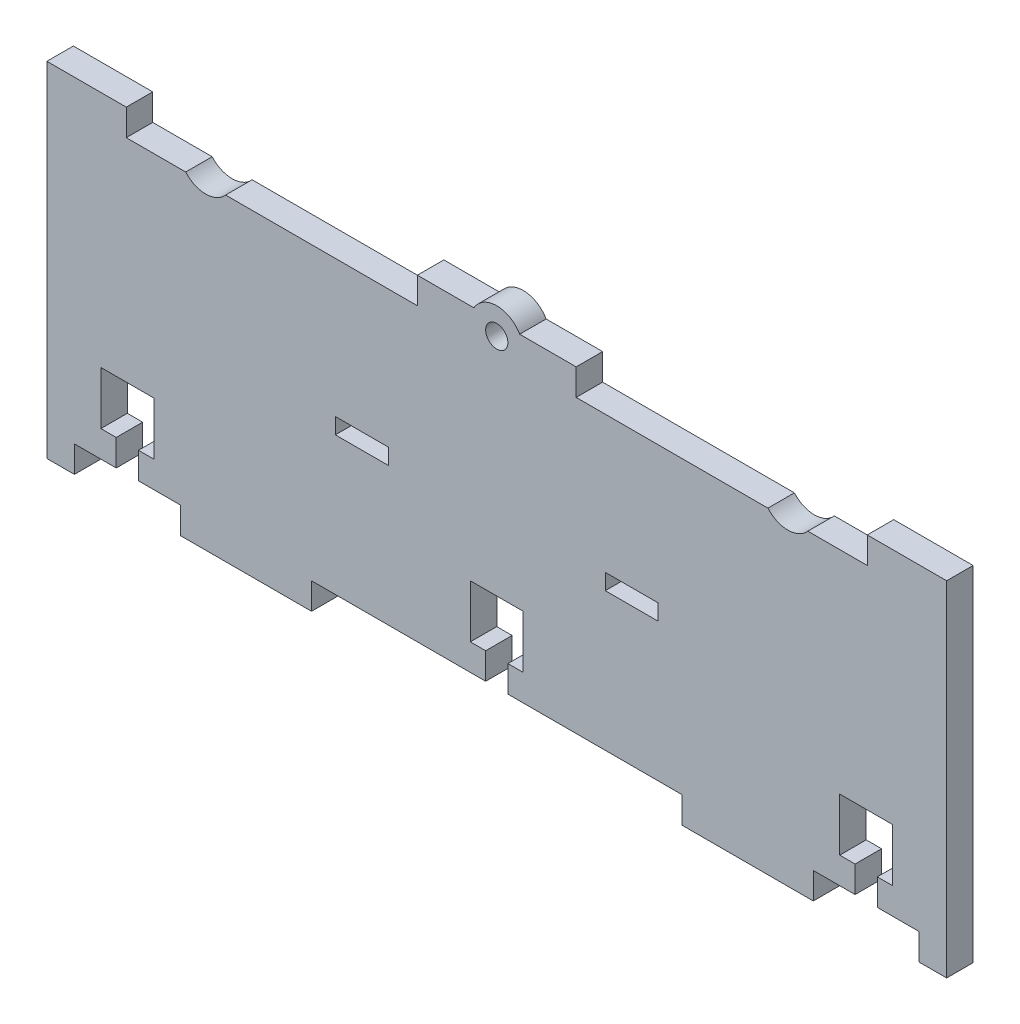
SolidWorks part; units mm, degrees
ref_plane "Front Plane" through (0, 0, 0) normal (0, 0, 1) x (1, 0, 0)
ref_plane "Top Plane" through (0, 0, 0) normal (0, 1, 0) x (1, 0, 0)
ref_plane "Right Plane" through (0, 0, 0) normal (1, 0, 0) x (0, 0, -1)
sketch "Sketch1" plane through (0, 0, 0) normal (0, 0, 1) x (1, 0, 0)
  line L0 (35, 0) -> (35, -5)
  line L1 (115, 0) -> (-115, 0)
  line L2 (0, 0) -> (0, 55) construction
  line L3 (115, 55) -> (-115, 55)
  line L4 (-115, 0) -> (-115, 55)
  line L5 (-115, 15) -> (-120, 15)
  line L6 (-115, 15) -> (-115, 40)
  line L7 (-115, 40) -> (-120, 40)
  line L8 (-120, 15) -> (-120, 40)
  line L9 (-100, 55) -> (-70, 55)
  line L10 (-100, 55) -> (-100, 60)
  line L11 (-100, 60) -> (-70, 60)
  line L12 (-70, 55) -> (-70, 60)
  line L13 (-95, 0) -> (-35, 0)
  line L14 (-95, 0) -> (-95, -5)
  line L15 (-95, -5) -> (-35, -5)
  line L16 (-35, 0) -> (-35, -5)
  line L17 (95, -5) -> (35, -5)
  line L18 (95, 0) -> (95, -5)
  line L19 (95, 0) -> (35, 0)
  line L20 (70, 55) -> (70, 60)
  line L21 (100, 60) -> (70, 60)
  line L22 (100, 55) -> (100, 60)
  line L23 (100, 55) -> (70, 55)
  line L24 (120, 15) -> (120, 40)
  line L25 (115, 40) -> (120, 40)
  line L26 (115, 15) -> (115, 40)
  line L27 (115, 15) -> (120, 15)
  line L28 (115, 0) -> (115, 55)
  point P9 (-120, 27.5)
  point P10 (0, 27.5)
  dimension "D1" = 115
  dimension "D2" = 55
  dimension "D3" = 5
  dimension "D4" = 25
  dimension "D5" = 30
  dimension "D6" = 15
  dimension "D7" = 5
  dimension "D8" = 5
  dimension "D9" = 60
  dimension "D10" = 20
extrude "Boss-Extrude1" add sketch "Sketch1" along normal blind 5 contours L1 L2 L3 L4 | L3 L22 L21 L20 | L18 L1 L0 L17 | L3 L12 L11 L10 | L16 L1 L14 L15 | L8 L5 L4 L7 | L3 L4 L1 L28 | L26 L25 L24 L27 region at (65, -2.5, 0) region at (-57.5, 27.5, 0) region at (-65, -2.5, 0) region at (85, 57.5, 0) region at (-85, 57.5, 0) region at (-117.5, 27.5, 0)
sketch "Sketch2" plane through (0, 0, 0) normal (0, 0, -1) x (-1, 0, 0)
  line L0 (120, 15) -> (120, 40) construction
  line L1 (85, -5) -> (120, -5)
  line L2 (85, -5) -> (85, 60)
  line L3 (85, 60) -> (120, 60)
  line L4 (120, -5) -> (120, 60)
  line L6 (95, -5) -> (35, -5) construction
  line L7 (0, 28.4281) -> (0, 15.5246) construction
  line L8 (-120, -5) -> (-120, 60)
  line L9 (-85, 60) -> (-120, 60)
  line L10 (-85, -5) -> (-85, 60)
  line L11 (-85, -5) -> (-120, -5)
  dimension "D1" = 35
  dimension "D2" = 35
  dimension "D3" = 65
extrude "Cut-Extrude1" cut sketch "Sketch2" against normal blind 10
sketch "Sketch3" plane through (0, 0, 0) normal (0, 0, -1) x (-1, 0, 0)
  line L0 (-70, 55) -> (70, 55) construction
  line L1 (-58.7707, 55) -> (-51.2293, 55)
  line L2 (0, 55) -> (0, 47.8155) construction
  line L3 (58.7707, 55) -> (51.2293, 55)
  line L5 (85, 60) -> (85, -5) construction
  arc A0 (-58.7707, 55) -> (-51.2293, 55) centre (-55, 58.2836) ccw
  arc A2 (58.7707, 55) -> (51.2293, 55) centre (55, 58.2836) cw
  line M7 (70, 55) -> (-70, 55)
  dimension "D1" = 5
  dimension "D2" = 26.2293
  dimension "D3" = 30
extrude "Cut-Extrude2" cut sketch "Sketch3" against normal blind 5 contours A2 M7 | L1 A0 region at (-55, 54.3022, 0)
sketch "Sketch4" plane through (0, 55, 0) normal (0, 1, 0) x (1, 0, 0)
  line L0 (51.2293, 0) -> (-51.2293, 0) construction
  line L1 (15, 0) -> (-15, 0)
  line L2 (15, 0) -> (15, -5)
  line L3 (15, -5) -> (-15, -5)
  line L4 (-15, 0) -> (-15, -5)
  line L5 (51.2293, -5) -> (-51.2293, -5) construction
  point P8 (0, 0)
  dimension "D1" = 30
  dimension "D2" = 15
extrude "Boss-Extrude2" add sketch "Sketch4" along normal blind 5
sketch "Sketch5" plane through (0, 0, 0) normal (0, 0, -1) x (-1, 0, 0)
  line L0 (-85, -5) -> (-35, -5) construction
  line L1 (-59.8, -5) -> (-79.8, -5)
  line L2 (-59.8, -5) -> (-59.8, 0)
  line L3 (-59.8, 0) -> (-79.8, 0)
  line L4 (-79.8, -5) -> (-79.8, 0)
  line L5 (-85, -5) -> (-85, 60) construction
  line L6 (0, 0) -> (0, 22.2278) construction
  line L7 (-35, 0) -> (35, 0) construction
  line L8 (79.8, -5) -> (79.8, 0)
  line L9 (59.8, 0) -> (79.8, 0)
  line L10 (59.8, -5) -> (59.8, 0)
  line L11 (59.8, -5) -> (79.8, -5)
  dimension "D1" = 20
  dimension "D2" = 5.2
extrude "Cut-Extrude3" cut sketch "Sketch5" against normal blind 5
sketch "Sketch6" plane through (0, 0, 0) normal (0, 0, -1) x (-1, 0, 0)
  line L0 (-15, 60) -> (15, 60) construction
  circle A0 centre (0, 57.5) radius 2.1
  dimension "D1" = 2.5
  dimension "D2" = 4.2
extrude "Cut-Extrude4" cut sketch "Sketch6" against normal blind 5
sketch "Sketch7" plane through (0, 0, 0) normal (0, 0, -1) x (-1, 0, 0)
  line L0 (-15, 60) -> (15, 60) construction
  line L1 (4.3301, 60) -> (-4.3301, 60)
  arc A0 (-4.3301, 60) -> (4.3301, 60) centre (0, 57.5) cw
  dimension "D1" = 5
extrude "Boss-Extrude3" add sketch "Sketch7" against normal blind 5
sketch "Sketch8" plane through (0, 0, 0) normal (0, 0, -1) x (-1, 0, 0)
  line L0 (79.8, 0) -> (59.8, 0) construction
  line L1 (67.7, 0) -> (71.9, 0)
  line L2 (67.7, 0) -> (67.7, 5)
  line L3 (67.7, 5) -> (71.9, 5)
  line L4 (71.9, 0) -> (71.9, 5)
  line L5 (0, 0) -> (0, 16.7932) construction
  line L6 (74.8, 5) -> (64.8, 5)
  line L7 (74.8, 5) -> (74.8, 15)
  line L8 (74.8, 15) -> (64.8, 15)
  line L9 (64.8, 5) -> (64.8, 15)
  line L10 (-64.8, 5) -> (-64.8, 15)
  line L11 (-74.8, 15) -> (-64.8, 15)
  line L12 (-74.8, 5) -> (-74.8, 15)
  line L13 (-74.8, 5) -> (-64.8, 5)
  line L14 (-71.9, 0) -> (-71.9, 5)
  line L15 (-67.7, 5) -> (-71.9, 5)
  line L16 (-67.7, 0) -> (-67.7, 5)
  line L17 (-67.7, 0) -> (-71.9, 0)
  line L18 (-35, 0) -> (35, 0) construction
  line L19 (-2.1, 0) -> (2.1, 0)
  line L20 (-2.1, 0) -> (-2.1, 5)
  line L21 (-2.1, 5) -> (2.1, 5)
  line L22 (2.1, 0) -> (2.1, 5)
  line L24 (-5, 5) -> (5, 5)
  line L25 (-5, 5) -> (-5, 15)
  line L26 (-5, 15) -> (5, 15)
  line L27 (5, 5) -> (5, 15)
  point P10 (69.8, 5)
  point P11 (69.8, 0)
  point P12 (69.8, 15)
  point P34 (0, 15)
  point P35 (0, 0)
  line M19 (-79.8, 0) -> (-59.8, 0)
  line M23 (-35, 0) -> (35, 0)
  line M27 (59.8, 0) -> (79.8, 0)
  dimension "D1" = 5
  dimension "D2" = 4.2
  dimension "D3" = 10
  dimension "D4" = 10
  dimension "D5" = 5
  dimension "D6" = 10
  dimension "D7" = 10
  dimension "D8" = 4.2
extrude "Cut-Extrude5" cut sketch "Sketch8" against normal blind 5 contours L12 L13 L10 L11 | L16 L13 L14 M19 | L5 L24 L27 L26 | L21 L5 L26 L25 L24 | L5 L19 L22 L24 | L5 L21 L20 M23 | L9 L6 L3 L7 L8 | L4 L3 L2 M27 region at (-69.8, 2.5, 0) region at (-69.8, 10, 0) region at (1.05, 2.5, 0) region at (-1.05, 2.5, 0) region at (2.5, 10, 0) region at (-2.5, 10, 0) region at (69.8, 10, 0) region at (69.8, 2.5, 0)
sketch "Sketch9" plane through (0, 0, 0) normal (0, 0, -1) x (-1, 0, 0)
  line L0 (-20.5, 27.7965) -> (-42.5, 27.7965) construction
  line L1 (-20.5, 27.7965) -> (-42.5, 27.7965) construction
  line L2 (0, 57.5) -> (0, 41.2875) construction
  line L3 (-30.5, 26.1252) -> (-20.5, 26.1252)
  line L4 (-30.5, 26.1252) -> (-30.5, 29.1252)
  line L5 (-30.5, 29.1252) -> (-20.5, 29.1252)
  line L6 (-20.5, 26.1252) -> (-20.5, 29.1252)
  line L7 (20.5, 26.1252) -> (20.5, 29.1252)
  line L8 (30.5, 29.1252) -> (20.5, 29.1252)
  line L9 (30.5, 26.1252) -> (30.5, 29.1252)
  line L10 (30.5, 26.1252) -> (20.5, 26.1252)
  dimension "D1" = 3
  dimension "D2" = 10
extrude "Cut-Extrude6" cut sketch "Sketch9" against normal blind 10
